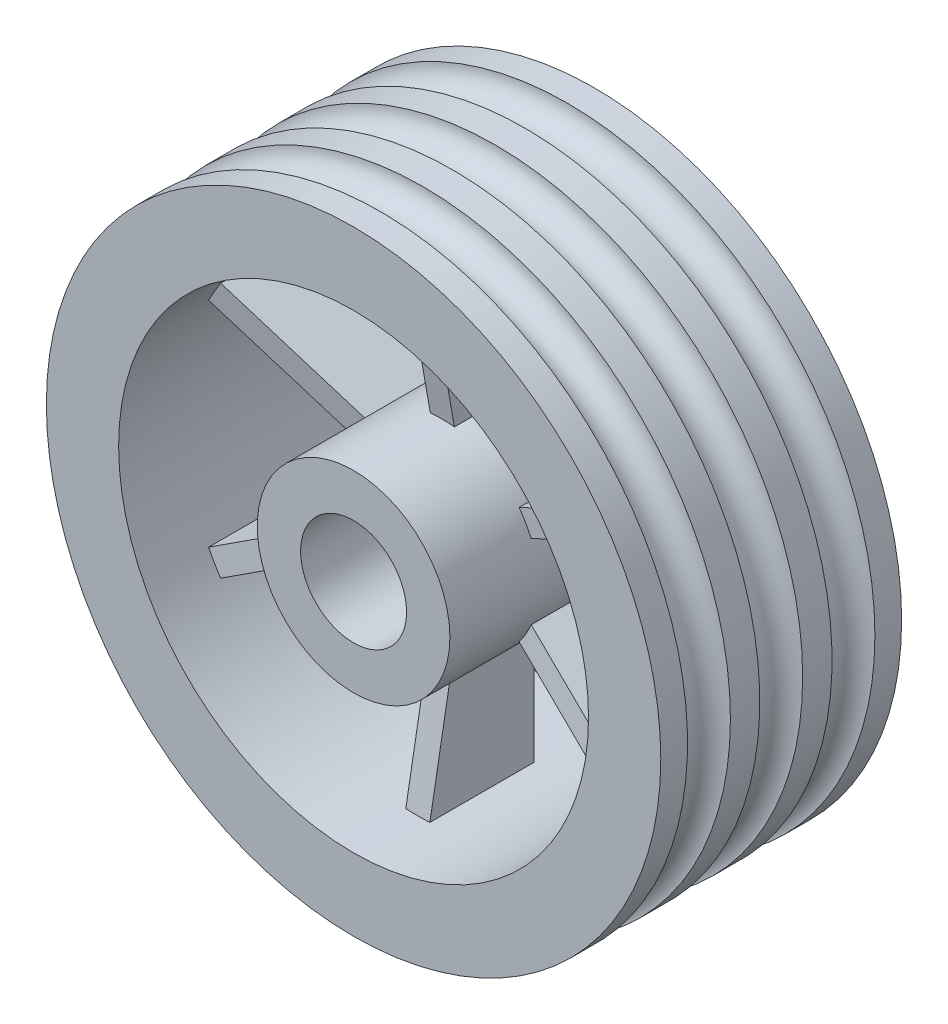
SolidWorks part; units mm, degrees
ref_plane "Front Plane" through (0, 0, 0) normal (0, 0, 1) x (1, 0, 0)
ref_plane "Top Plane" through (0, 0, 0) normal (0, 1, 0) x (1, 0, 0)
ref_plane "Right Plane" through (0, 0, 0) normal (1, 0, 0) x (0, 0, -1)
sketch "Sketch1" plane through (0, 0, 0) normal (0, 0, 1) x (1, 0, 0)
  circle A0 centre (0, 0) radius 9.755
  circle A1 centre (0, 0) radius 12.755
  dimension "D2" = 25.51
  dimension "D1" = 3
extrude "Boss-Extrude1" add sketch "Sketch1" along normal blind 10
sketch "Sketch2" plane through (0, 0, 0) normal (0, 0, 1) x (1, 0, 0)
  circle A0 centre (0, 0) radius 4
  circle A1 centre (0, 0) radius 2.2
  dimension "D1" = 8
  dimension "D2" = 4.4
extrude "Boss-Extrude2" add sketch "Sketch2" along normal up to surface (10 mm away) and the other way blind 0.5 separate body up to face at (12.755, 0, 10)
sketch "Sketch5" plane through (0, 0, 0) normal (1, 0, 0) x (0, 0, -1)
  line L6 (-3, 2.2) -> (-3, 10.7)
  line L7 (-3, 10.7) -> (-7.5, 10.7)
  line L8 (-7.5, 10.7) -> (-6, 2.2)
  line L9 (-6, 2.2) -> (-3, 2.2)
  dimension "D1" = 2.2
  dimension "D2" = 3
  dimension "D3" = 3
  dimension "D4" = 4.5
  dimension "D5" = 8.5
extrude "Boss-Extrude3" add sketch "Sketch5" along normal blind 0.5 and the other way blind 0.5
sketch "Sketch6" plane through (0, 0, 0) normal (1, 0, 0) x (0, 0, -1)
  line L0 (0, 0) -> (-10, 0) construction
  line L1 (-10, 2.2) -> (-10, -2.2) construction
  line L2 (-10, 0) -> (-10, 5) construction
  line L3 (-10, 5) -> (-10, 9.755)
  line L4 (-10, 12.755) -> (-10, -12.755) construction
  line L5 (-10, 9.755) -> (-10, -9.755) construction
  line L7 (-8.5, 5) -> (-8.5, 9.755)
  line L8 (-8.5, 9.755) -> (-10, 9.755)
  line L9 (-10, 5) -> (-10, 3.4839)
  line L10 (-10, 3.4839) -> (-8.5, 3.4839)
  line L11 (-8.5, 3.4839) -> (-8.5, 5)
  dimension "D1" = 5
  dimension "D2" = 1.5
  dimension "D3" = 4.755
extrude "Boss-Extrude8" [suppressed] add sketch "Sketch6" along normal blind 0.5 and the other way blind 0.5
pattern_circular "CirPattern1" count 6 over 360 about axis through (0, 0, -0.5) along (0, 0, 1) of "Boss-Extrude3", "Boss-Extrude8" reverse direction yes
sketch "Sketch7" plane through (0, 0, 0) normal (1, 0, 0) x (0, 0, -1)
  line L0 (0, 0) -> (0, 12.755) construction
  line L2 (0, -12.755) -> (0, 12.755) construction
  line L3 (0, 12.755) -> (-10, 12.755) construction
  line L4 (-10, 12.755) -> (-10, -12.755) construction
  line L5 (0, 0) -> (-10.5402, 0) construction
  circle A0 centre (-5, 12.755) radius 0.89
  circle A1 centre (-2, 12.755) radius 0.89
  circle A2 centre (-8, 12.755) radius 0.89
  dimension "D3" = 1.78
  dimension "D1" = 12.755
  dimension "D2" = 10
  dimension "D6" = 3
  dimension "D7" = 3
  dimension "D4" = 2
  dimension "D5" = 2
revolve "Cut-Revolve1" cut sketch "Sketch7" angle 360 about L5
ref_plane "Plane1" through (0, 0, 2) normal (0, 0, -1) x (-1, 0, 0)
ref_plane "Plane2" through (0, 0, 5) normal (0, 0, -1) x (-1, 0, 0)
ref_plane "Plane3" through (0, 0, 8) normal (0, 0, -1) x (-1, 0, 0)
ref_plane "Plane4" through (0, 0, 0) normal (0, 0, -1) x (-1, 0, 0)
